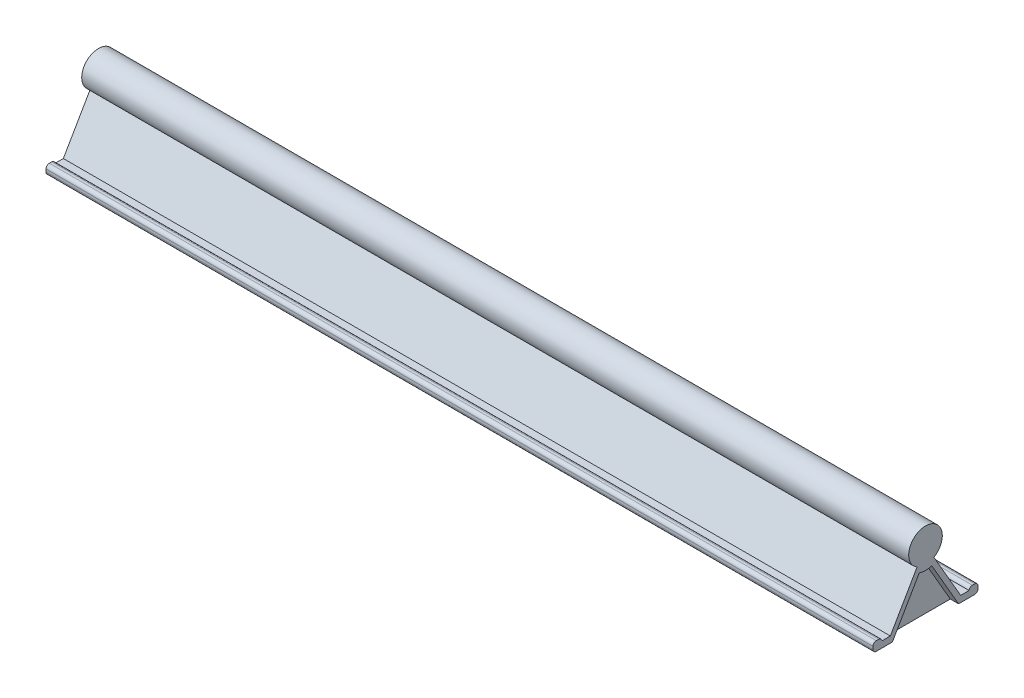
SolidWorks part; units mm, degrees
ref_plane "Front Plane" through (0, 0, 0) normal (0, 0, 1) x (1, 0, 0)
ref_plane "Top Plane" through (0, 0, 0) normal (0, 1, 0) x (1, 0, 0)
ref_plane "Right Plane" through (0, 0, 0) normal (1, 0, 0) x (0, 0, -1)
sketch "Sketch1" plane through (0, 0, 0) normal (1, 0, 0) x (0, 0, -1)
  line L0 (0, 0) -> (0, 40.64) construction
  line L1 (0, 50.8) -> (67.1648, 50.8) construction
  line L2 (1000, 30.48) -> (5.8659, 30.48) construction
  line L3 (-21.2638, 3.81) -> (-5.08, 31.8412)
  line L4 (5.08, 31.8412) -> (21.2638, 3.81)
  line L5 (-21.2638, 3.81) -> (-26.3438, 3.81)
  line L6 (-26.3438, 3.81) -> (-26.3438, 5.588)
  line L7 (-26.3438, 5.588) -> (-31.75, 5.588)
  line L8 (-31.75, 5.588) -> (-31.75, 0)
  line L9 (-31.75, 0) -> (31.75, 0)
  line L10 (31.75, 5.588) -> (31.75, 0)
  line L11 (26.3438, 5.588) -> (31.75, 5.588)
  line L12 (26.3438, 3.81) -> (26.3438, 5.588)
  line L13 (21.2638, 3.81) -> (26.3438, 3.81)
  line L14 (-5.8659, 30.48) -> (-18.71, 30.48) construction
  arc A0 (5.08, 31.8412) -> (-5.08, 31.8412) centre (0, 40.64) ccw
  point P11 (-27.533, 4.4784)
  point P18 (0, 0)
  point P22 (-22.8411, 3.6181)
  point P23 (-26.7402, 2.3985)
  point P24 (0, 0)
  point P25 (-27.5702, 3.7372)
  point P26 (23.5452, 1.5584)
  point P27 (-29.2819, 3.922)
  point P28 (-27.1368, 6.2466)
  point P29 (-31.75, 6.919)
  point P30 (0, 0)
  dimension "D1" = 30.48
  dimension "D2" = 20.32
  dimension "D3" = 60
  dimension "D4" = 63.5
  dimension "D5" = 5.08
  dimension "D6" = 3.81
  dimension "D7" = 5.588
extrude "Boss-Extrude1" add sketch "Sketch1" along normal blind 500
sketch "Sketch2" plane through (0, 0, 0) normal (-1, 0, 0) x (0, 0, 1)
  line L0 (18.2674, 3) -> (18.2674, 3)
  line L1 (18.2674, 3) -> (3.8087, 28.0432)
  line L2 (-3.8087, 28.0432) -> (-18.2674, 3)
  line L3 (-18.2674, 3) -> (-18.2674, 3)
  line L4 (-18.2674, 3) -> (-18.2674, 3)
  line L5 (-18.2674, 3) -> (-18.2674, 3)
  line L6 (-18.2674, 3) -> (-18.2674, 3)
  line L8 (18.2674, 3) -> (18.2674, 3)
  line L9 (18.2674, 3) -> (18.2674, 3)
  line L10 (18.2674, 3) -> (18.2674, 3)
  line L11 (26.3438, 3.81) -> (21.2638, 3.81)
  line L12 (21.2638, 3.81) -> (5.08, 31.8412)
  line L13 (-5.08, 31.8412) -> (-21.2638, 3.81)
  line L14 (-21.2638, 3.81) -> (-26.3438, 3.81)
  line L15 (-26.3438, 3.81) -> (-26.3438, 5.588)
  line L16 (-26.3438, 5.588) -> (-31.75, 5.588)
  line L17 (-31.75, 5.588) -> (-31.75, 0)
  line L18 (-31.75, 0) -> (31.75, 0)
  line L19 (31.75, 0) -> (31.75, 5.588)
  line L20 (31.75, 5.588) -> (26.3438, 5.588)
  line L21 (26.3438, 5.588) -> (26.3438, 3.81)
  line L22 (26.3438, 3.81) -> (21.2638, 3.81) construction
  line L23 (21.2638, 3.81) -> (5.08, 31.8412) construction
  line L24 (-5.08, 31.8412) -> (-21.2638, 3.81) construction
  line L25 (-21.2638, 3.81) -> (-26.3438, 3.81) construction
  line L26 (-26.3438, 3.81) -> (-26.3438, 5.588) construction
  line L27 (-26.3438, 5.588) -> (-31.75, 5.588) construction
  line L28 (-31.75, 5.588) -> (-31.75, 0) construction
  line L29 (-31.75, 0) -> (31.75, 0) construction
  line L30 (31.75, 0) -> (31.75, 5.588) construction
  line L31 (31.75, 5.588) -> (26.3438, 5.588) construction
  line L32 (26.3438, 5.588) -> (26.3438, 3.81) construction
  line L33 (18.2674, 3) -> (0.6525, 33.5098) construction
  line L34 (-0.6525, 33.5098) -> (-18.2674, 3) construction
  line L35 (-18.2674, 3) -> (-19.9994, 0)
  line L36 (18.2674, 3) -> (19.9994, 0)
  line L37 (19.9994, 0) -> (-19.9994, 0)
  line L39 (-18.2674, 3) -> (18.2674, 3) construction
  arc A1 (5.08, 31.8412) -> (-5.08, 31.8412) centre (0, 40.64) ccw
  arc A2 (5.08, 31.8412) -> (-5.08, 31.8412) centre (0, 40.64) ccw construction
  arc A3 (0.6525, 33.5098) -> (-0.6525, 33.5098) centre (0, 40.64) ccw construction
  arc A5 (-3.8087, 28.0432) -> (3.8087, 28.0432) centre (0, 40.64) ccw
  line M23 (-31.75, 0) -> (31.75, 0)
  dimension "D3" = 3
  dimension "D1" = 0
  dimension "D2" = 3
extrude "Cut-Extrude1" cut sketch "Sketch2" against normal blind 5 contours A5 L2 L35 L36 L1 M23 region at (0, 10.7698, 0)
ref_plane "Plane4" through (250, 0, 0) normal (-1, 0, 0) x (0, 0, 1)
mirror "Mirror1" about plane through (250, 0, 0) normal (-1, 0, 0) of "Cut-Extrude1"
fillet "Fillet1" radius 2 6 edges at (250, 0, 31.75) (250, 5.588, 26.3438) (250, 5.588, 31.75) (250, 0, -31.75) (250, 5.588, -31.75) (250, 5.588, -26.3438)
